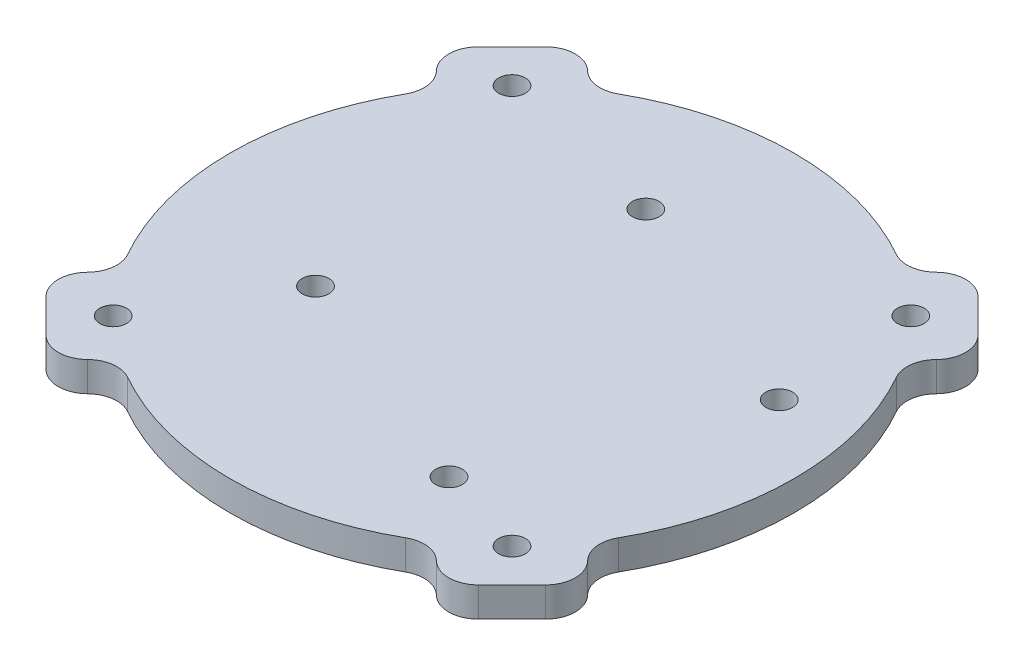
SolidWorks part; units mm, degrees
material "6061-T6 (SS)"
ref_plane "Front Plane" through (0, 0, 0) normal (0, 0, 1) x (1, 0, 0)
ref_plane "Top Plane" through (0, 0, 0) normal (0, 1, 0) x (1, 0, 0)
ref_plane "Right Plane" through (0, 0, 0) normal (1, 0, 0) x (0, 0, -1)
sketch "Sketch3" plane through (0, 0, 0) normal (0, 1, 0) x (1, 0, 0)
  line L0 (0, 0) -> (-33.5876, -33.5876) construction
  line L1 (-33.5876, -33.5876) -> (33.5876, 33.5876) construction
  line L2 (0, 0) -> (-33.5876, 33.5876) construction
  line L3 (-33.5876, 33.5876) -> (33.5876, -33.5876) construction
  line L4 (47.5, 0) -> (0, 0) construction
  line L9 (36.416, 42.0729) -> (42.0729, 36.416)
  line L10 (42.0729, 29.3449) -> (32.8805, 20.1525)
  line L11 (32.8805, 20.1525) -> (20.1525, 32.8805)
  line L12 (20.1525, 32.8805) -> (29.3449, 42.0729)
  line L13 (42.0729, -36.416) -> (36.416, -42.0729)
  line L14 (29.3449, -42.0729) -> (20.1525, -32.8805)
  line L15 (20.1525, -32.8805) -> (32.8805, -20.1525)
  line L16 (32.8805, -20.1525) -> (42.0729, -29.3449)
  line L17 (-36.416, -42.0729) -> (-42.0729, -36.416)
  line L18 (-42.0729, -29.3449) -> (-32.8805, -20.1525)
  line L19 (-32.8805, -20.1525) -> (-20.1525, -32.8805)
  line L20 (-20.1525, -32.8805) -> (-29.3449, -42.0729)
  line L21 (-42.0729, 36.416) -> (-36.416, 42.0729)
  line L22 (-29.3449, 42.0729) -> (-20.1525, 32.8805)
  line L23 (-20.1525, 32.8805) -> (-32.8805, 20.1525)
  line L24 (-32.8805, 20.1525) -> (-42.0729, 29.3449)
  circle A0 centre (0, 0) radius 47.5
  circle A2 centre (0, 0) radius 55.5 construction
  circle A3 centre (0, 0) radius 47.5 construction
  circle A4 centre (0, 0) radius 30 construction
  arc A5 (42.0729, 36.416) -> (42.0729, 29.3449) centre (38.5373, 32.8805) cw
  arc A6 (36.416, 42.0729) -> (29.3449, 42.0729) centre (32.8805, 38.5373) ccw
  circle A7 centre (33.5876, 33.5876) radius 2.25
  arc A8 (36.416, -42.0729) -> (29.3449, -42.0729) centre (32.8805, -38.5373) cw
  arc A9 (42.0729, -36.416) -> (42.0729, -29.3449) centre (38.5373, -32.8805) ccw
  circle A10 centre (33.5876, -33.5876) radius 2.25
  circle A11 centre (0, 0) radius 47.5
  arc A12 (-42.0729, -36.416) -> (-42.0729, -29.3449) centre (-38.5373, -32.8805) cw
  arc A13 (-36.416, -42.0729) -> (-29.3449, -42.0729) centre (-32.8805, -38.5373) ccw
  circle A14 centre (-33.5876, -33.5876) radius 2.25
  circle A15 centre (0, 0) radius 47.5
  arc A16 (-36.416, 42.0729) -> (-29.3449, 42.0729) centre (-32.8805, 38.5373) cw
  arc A17 (-42.0729, 36.416) -> (-42.0729, 29.3449) centre (-38.5373, 32.8805) ccw
  circle A18 centre (-33.5876, 33.5876) radius 2.25
  circle A19 centre (0, 0) radius 47.5
  point P5 (55.5, 0)
  point P13 (33.5876, 33.5876)
  point P19 (39.3431, 26.6152)
  point P21 (39.2444, 39.2444)
  point P28 (33.5876, -33.5876)
  point P31 (26.6152, -39.3431)
  point P41 (-33.5876, -33.5876)
  point P44 (-39.3431, -26.6152)
  point P54 (-33.5876, 33.5876)
  point P57 (-26.6152, 39.3431)
  point P65 (0, 0)
  dimension "D1" = 95
  dimension "D2" = 111
  dimension "D4" = 95
  dimension "D5" = 60
  dimension "D8" = 5
  dimension "D9" = 4.5
  dimension "D3" = 45
  dimension "D6" = 55.5
  dimension "D7" = 18
  dimension "D10" = 18
  dimension "D11" = 4
extrude "Boss-Extrude2" add sketch "Sketch3" along normal blind 5 contours A14 A0 L20 L19 L18 | A14 A0 L18 A12 L17 A13 L20 | A10 A0 L14 A8 L13 A9 L16 | A18 A0 L24 L23 L22 | A18 A0 L22 A16 L21 A17 L24 | L16 A0 L10 L11 L12 L22 L23 L24 L18 L19 L20 L14 L15 | A7 A0 L10 A5 L9 A6 L12 | A7 A0 L12 L11 L10 | A10 A0 L16 L15 L14 region at (36.2625, 0, -36.2625) region at (29.8142, 0, -29.8142) region at (0, 0, 0) region at (-36.2625, 0, -36.2625) region at (-29.8142, 0, -29.8142) region at (29.8142, 0, 29.8142) region at (36.2625, 0, 36.2625) region at (-36.2625, 0, 36.2625) region at (-29.8142, 0, 29.8142)
fillet "Fillet2" radius 5 8 edges at (26.6152, 2.5, 39.3431) (-26.6152, 2.5, 39.3431) (-39.3431, 2.5, 26.6152) (-39.3431, 2.5, -26.6152) (-26.6152, 2.5, -39.3431) (26.6152, 2.5, -39.3431) (39.3431, 2.5, -26.6152) (39.3431, 2.5, 26.6152)
sketch "Sketch4" plane through (0, 5, 0) normal (0, 1, 0) x (1, 0, 0)
  line L0 (-20.8827, -12.214) -> (34.7466, 10.2666) construction
  line L1 (18.1722, -28.7884) -> (-4.3083, 26.841) construction
  circle A0 centre (6.9319, -0.9737) radius 30 construction
  circle A3 centre (6.9319, -0.9737) radius 30 construction
  circle A5 centre (6.9319, -0.9737) radius 30 construction
  circle A7 centre (6.9319, -0.9737) radius 30 construction
  circle A9 centre (6.9319, -0.9737) radius 30 construction
  circle A11 centre (6.9319, -0.9737) radius 30 construction
  circle A12 centre (-20.8827, -12.214) radius 2.25
  circle A13 centre (-4.3083, 26.841) radius 2.25
  circle A14 centre (6.9319, -0.9737) radius 30 construction
  circle A15 centre (34.7466, 10.2666) radius 2.25
  circle A16 centre (6.9319, -0.9737) radius 30 construction
  circle A17 centre (18.1722, -28.7884) radius 2.25
  circle A18 centre (6.9319, -0.9737) radius 30 construction
  point P22 (6.9319, -0.9737)
  point P24 (6.9319, -0.9737)
  dimension "D1" = 60
  dimension "D2" = 4.5
  dimension "D3" = 6
sketch "Sketch6" plane through (0, 0, 0) normal (0, -1, 0) x (1, 0, 0)
  circle A0 centre (0, 0) radius 5.284 construction
extrude "Cut-Extrude1" cut sketch "Sketch4" against normal through all
equation "\"D1@Sketch3\"=\"MDECK_OD\""
equation "\"D2@Sketch3\"=\"MDECK_TowerEarOuterRadius\"*2"
equation "\"D4@Sketch3\"=\"UTR_BCD\""
equation "\"D5@Sketch3\"=\"MDECK_MountPatternBCD\""
equation "\"D7@Sketch3\"=\"MDECK_TowerEarTangentialWidth\""
equation "\"D9@Sketch3\"=4.5"
equation "\"D10@Sketch3\"=\"MDECK_TowerEarTangentialWidth\""
equation "\"D1@Boss-Extrude2\"=\"MDECK_Thk\""
equation "\"D1@Sketch4\"=\"MDECK_BracketMountBCD\""
equation "\"____ GENERATED PART EXPORTS ____\" = 0"
equation "\"SYS_VersionTag\" = 2"
equation "\"MDECK_OD\" = 95mm"
equation "\"MDECK_Thk\" = 5mm"
equation "\"UTR_BCD\" = 95mm"
equation "\"UTR_Count\" = 4"
equation "\"MDECK_IsMotorBaseOnly\" = 1"
equation "\"MDECK_DirectMotorFaceMountDisabled\" = 1"
equation "\"MDECK_MotorSupportPocketEnabled\" = 1"
equation "\"MDECK_MotorSupportPocketDia\" = 34.6mm"
equation "\"MDECK_MotorSupportPocketDepth\" = 1.5mm"
equation "\"MDECK_MotorSupportPocketSupportOD\" = 42mm"
equation "\"MDECK_BracketMountBCD\" = 60mm"
equation "\"MDECK_BracketMountClearDia\" = 4.5mm"
equation "\"MDECK_BracketMountCount\" = 4"
equation "\"MDECK_ServiceSlotWidth\" = 8mm"
equation "\"MDECK_ServiceSlotLength\" = 12mm"
equation "\"MDECK_ServiceSlotSectorDeg\" = 300"
equation "\"MDECK_TowerInterfaceUsesPerimeterEars\" = 1"
equation "\"MDECK_TowerEarCount\" = 4"
equation "\"MDECK_TowerEarPatternBCD\" = 95mm"
equation "\"MDECK_TowerEarOuterRadius\" = 55.5mm"
equation "\"MDECK_TowerEarTangentialWidth\" = 18mm"
equation "\"MDECK_TowerEarBlendR\" = 5mm"
equation "\"MDECK_MountPatternBCD\" = 60mm"
equation "\"MDECK_MountPatternHoleClearDia\" = 4.5mm"
equation "\"MDECK_MountPatternHoleCount\" = 4"
